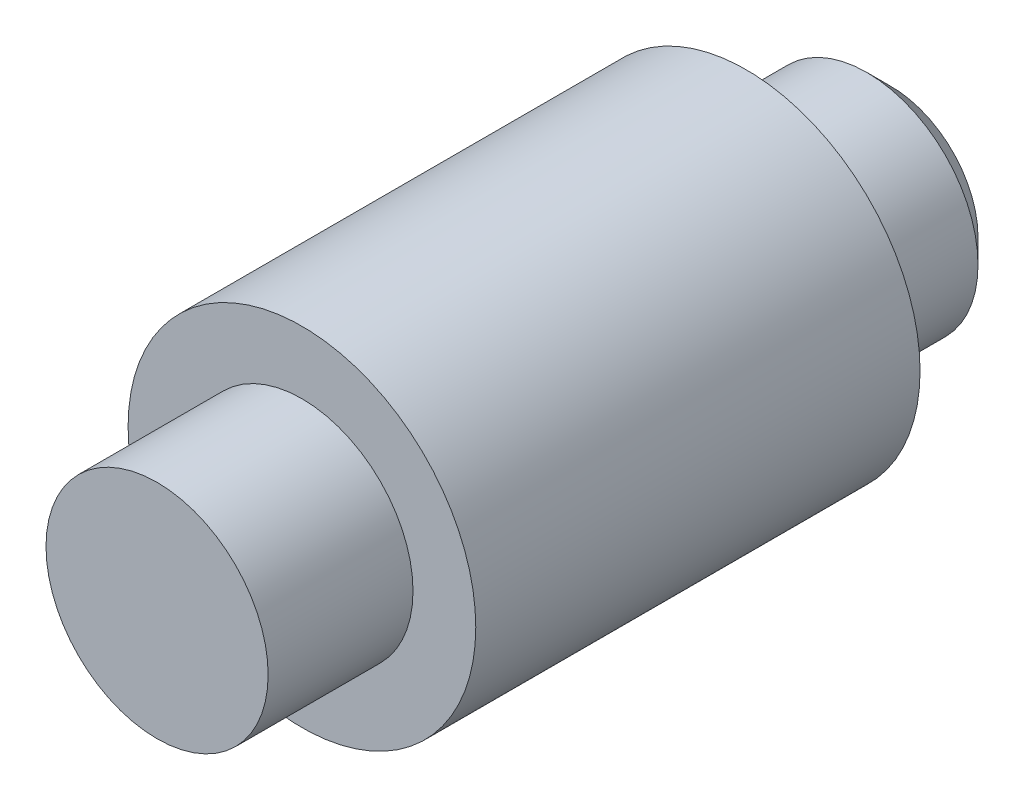
SolidWorks part; units mm, degrees
ref_plane "Front Plane" through (0, 0, 0) normal (0, 0, 1) x (1, 0, 0)
ref_plane "Top Plane" through (0, 0, 0) normal (0, 1, 0) x (1, 0, 0)
ref_plane "Right Plane" through (0, 0, 0) normal (1, 0, 0) x (0, 0, -1)
sketch "Sketch2" plane through (0, 0, 0) normal (0, 0, 1) x (1, 0, 0)
  circle A0 centre (0, 0) radius 1.25
  dimension "D1" = 2.5
sketch "Sketch3" plane through (0, 0, 0) normal (0, 0, 1) x (1, 0, 0)
  line L5 (-3.6, 3.6) -> (3.6, 3.6) construction
  line L6 (-3.6, 3.6) -> (-3.6, -3.6) construction
  line L7 (-3.6, -3.6) -> (3.6, -3.6) construction
  line L8 (3.6, 3.6) -> (3.6, -3.6) construction
  circle A0 centre (0, 0) radius 3.6
  point P4 (0, 3.6)
  point P6 (-3.6, 0)
  dimension "D1" = 7.2
extrude "Boss-Extrude1" add sketch "Sketch3" along normal blind 9.2
sketch "Sketch4" plane through (0, 0, 0) normal (0, 0, 1) x (1, 0, 0)
  circle A0 centre (0, 0) radius 2.3
  dimension "D1" = 4.6
extrude "Boss-Extrude2" add sketch "Sketch4" against normal blind 3
sketch "Sketch5" plane through (0, 0, 9.2) normal (0, 0, 1) x (1, 0, 0)
  circle A0 centre (0, 0) radius 2.3
  dimension "D1" = 4.6
extrude "Boss-Extrude3" add sketch "Sketch5" along normal blind 3
chamfer "Chamfer1" distance 0.5 angle 45 1 edges at (2.3, 0, -3)
equation "\"length\"=9.2"
equation "\"D1@Boss-Extrude1\"=\"length\""
equation "\"hole\"=4.6"
equation "\"D1@Sketch5\"=\"hole\""
equation "\"D1@Sketch4\"=\"hole\""
equation "\"foot\"=3"
equation "\"D1@Boss-Extrude3\"=\"foot\""
equation "\"D1@Boss-Extrude2\"=\"foot\""
